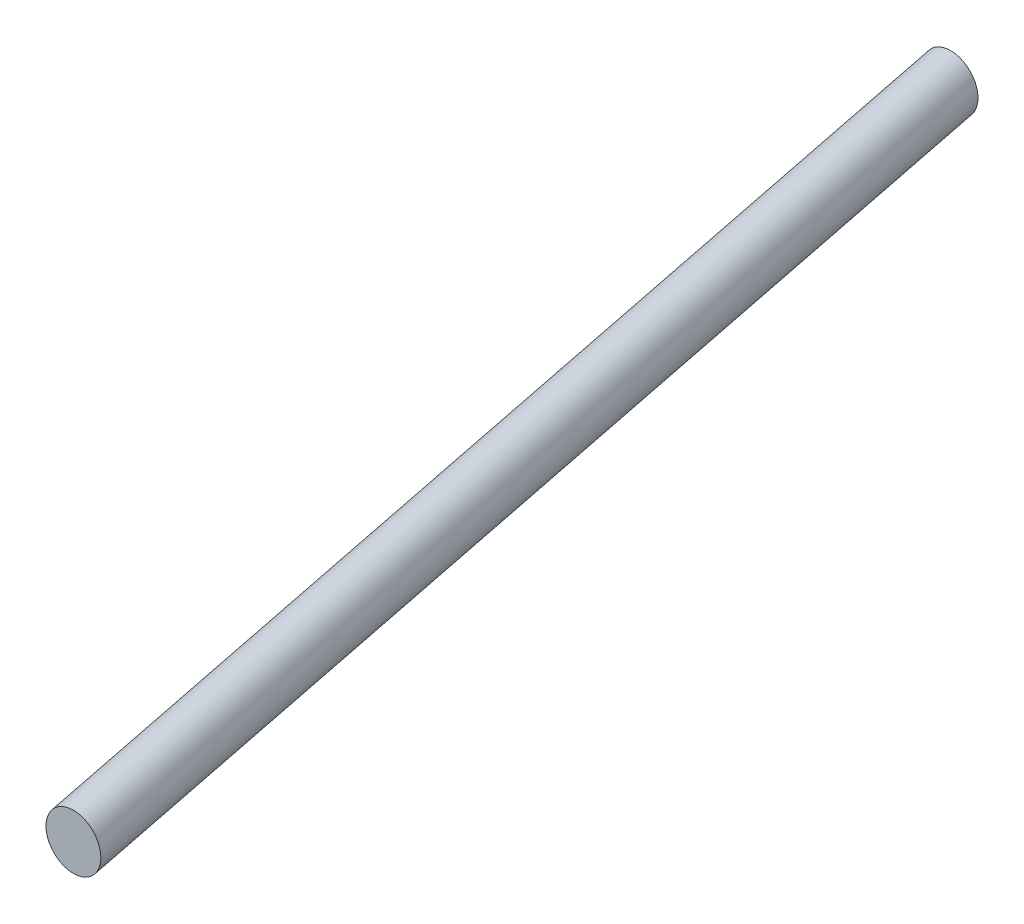
SolidWorks part; units mm, degrees
material "Balsa"
ref_plane "Alzado" through (0, 0, 0) normal (0, 0, 1) x (1, 0, 0)
ref_plane "Planta" through (0, 0, 0) normal (0, 1, 0) x (1, 0, 0)
ref_plane "Vista lateral" through (0, 0, 0) normal (1, 0, 0) x (0, 0, -1)
sketch "Croquis3" plane through (0, 0, 0) normal (0, 0, 1) x (1, 0, 0)
  line L0 (0, 0) -> (0, 2.5) construction
  circle A0 centre (0, 0) radius 2.5
  dimension "D1" = 5
ref_plane "Plano1" through (0, 0, 100) normal (0, 0, 1) x (1, 0, 0)
sketch "Croquis4" plane through (0, 0, 100) normal (0, 0, 1) x (1, 0, 0)
  line L0 (0, 0) -> (20, 0) construction
  line L1 (20, 0) -> (20, 2.5) construction
  circle A0 centre (20, 0) radius 2.5
  dimension "D2" = 5
  dimension "D1" = 20
loft "Recubrir1" add profiles "Croquis3", "Croquis4" connector at (-0.0298, 2.4998, 0) connector at (20.0236, 2.4999, 100)
sketch "Croquis5" plane through (0, 0, 100) normal (0, 0, 1) x (1, 0, 0)
  line L0 (20, 0) -> (22.5, 0) construction
  circle A0 centre (20, 0) radius 2.5 construction
  circle A1 centre (20, 0) radius 2.5 construction
